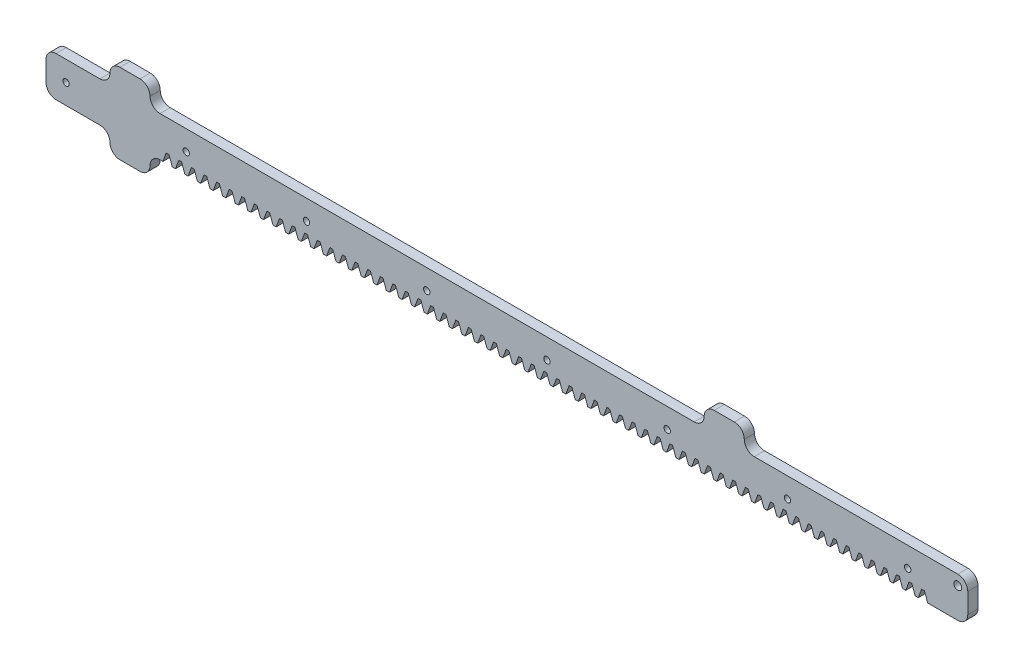
SolidWorks part; units mm, degrees
material "PC High Viscosity"
ref_plane "Front Plane" through (0, 0, 0) normal (0, 0, 1) x (1, 0, 0)
ref_plane "Top Plane" through (0, 0, 0) normal (0, 1, 0) x (1, 0, 0)
ref_plane "Right Plane" through (0, 0, 0) normal (1, 0, 0) x (0, 0, -1)
sketch "Sketch1" plane through (0, 0, 0) normal (0, 0, 1) x (1, 0, 0)
  line L1 (0, 0) -> (40.5308, 0)
  line L2 (0, 0) -> (0, 25.4)
  line L3 (0, 25.4) -> (40.5308, 25.4)
  line L4 (584.2, 0) -> (584.2, 25.4)
  line L7 (533.4, 25.4) -> (584.2, 25.4)
  line L8 (65.9308, 25.4) -> (417.1409, 25.4)
  line L9 (65.9308, 0) -> (584.2, 0)
  line L11 (584.2, 22.7162) -> (577.85, 26.3823) construction
  line L12 (577.85, 26.3823) -> (571.5, 22.7162) construction
  line L13 (571.5, 22.7162) -> (571.5, 15.3838) construction
  line L14 (571.5, 15.3838) -> (577.85, 11.7177) construction
  line L15 (577.85, 11.7177) -> (584.2, 15.3838) construction
  line L16 (584.2, 15.3838) -> (584.2, 22.7162) construction
  line L19 (590.55, 0) -> (590.55, 10.0162) construction
  line L20 (590.55, 10.0162) -> (76.2, 10.0162) construction
  line L21 (76.2, 10.0162) -> (76.2, 0) construction
  line L22 (442.5409, 25.4) -> (533.4, 25.4)
  line L23 (40.5308, 25.4) -> (40.5308, 38.1)
  line L24 (40.5308, 38.1) -> (65.9308, 38.1)
  line L25 (65.9308, 38.1) -> (65.9308, 25.4)
  line L26 (40.5308, 0) -> (40.5308, -12.7)
  line L27 (40.5308, -12.7) -> (65.9308, -12.7)
  line L28 (65.9308, -12.7) -> (65.9308, 0)
  line L29 (417.1409, 25.4) -> (417.1409, 38.1)
  line L30 (417.1409, 38.1) -> (442.5409, 38.1)
  line L31 (442.5409, 38.1) -> (442.5409, 25.4)
  circle A0 centre (577.85, 19.05) radius 2.4892
  circle A1 centre (577.85, 19.05) radius 6.35 construction
  point P6 (0, 0)
  point P7 (40.5308, 0)
  point P10 (577.85, 26.7355)
  point P29 (0, 0)
  dimension "D5" = 4.9784
  dimension "D6" = 25.4
  dimension "D7" = 12.7
  dimension "D1" = 584.2
  dimension "D2" = 25.4
  dimension "D3" = 167.0591
  dimension "D4" = 40.5308
  dimension "D8" = 12.7
extrude "Boss-Extrude1" add sketch "Sketch1" along normal blind 6.477 contours L3 | L1 L4 L3 L2 A0 | L1 region at (284.8004, 13.0814, 0)
fillet "Fillet2" radius 6.35 16 edges at (0, 0, 3.2385) (0, 25.4, 3.2385) (584.2, 25.4, 3.2385) (417.1409, 38.1, 3.2385) (442.5409, 38.1, 3.2385) (40.5308, 38.1, 3.2385) (65.9308, 38.1, 3.2385) (40.5308, 25.4, 3.2385) (40.5308, 0, 3.2385) (584.2, 0, 3.2385) (65.9308, 0, 3.2385) (65.9308, -12.7, 3.2385) (40.5308, -12.7, 3.2385) (65.9308, 25.4, 3.2385) (442.5409, 25.4, 3.2385) (417.1409, 25.4, 3.2385)
sketch "Sketch2" plane through (0, 0, 6.477) normal (0, 0, 1) x (1, 0, 0)
  line L0 (558.8, 0) -> (72.2808, 0)
  line L1 (72.2808, 0) -> (72.2808, 5.715)
  line L2 (72.2808, 5.715) -> (558.8, 5.715)
  line L3 (558.8, 5.715) -> (558.8, 0)
  line L5 (557.8755, 2.54) -> (549.711, 2.54) construction
  line L6 (558.8, 0) -> (556.7199, 5.715)
  line L8 (552.8688, 0) -> (558.8, 0)
  line L10 (556.7199, 5.715) -> (554.9488, 5.715)
  line L11 (558.8, 0) -> (552.8688, 0)
  line L12 (552.8688, 0) -> (554.9488, 5.715)
  line L13 (554.9488, 5.715) -> (556.7199, 5.715)
  line L14 (558.8, 0) -> (552.8688, 0)
  line L15 (554.9488, 5.715) -> (556.7199, 5.715)
  line L16 (558.8, 0) -> (552.8688, 0)
  line L17 (552.8688, 0) -> (558.8, 0)
  line L19 (556.7199, 5.715) -> (554.9488, 5.715) construction
  line L20 (552.8688, 0) -> (558.8, 0) construction
  line L21 (0, 0) -> (40.5308, 0) construction
  line L22 (584.2, 0) -> (584.2, 25.4) construction
  line L23 (65.9308, 0) -> (584.2, 0) construction
  point P8 (553.7932, 2.54)
  point P13 (552.8688, 0)
  point P15 (0, 0)
  point P16 (557.8755, 2.54)
  point P17 (571.6333, 0)
  point P21 (572.7128, -2.7117)
  point P22 (0, 0)
  point P23 (0, 0)
  point P24 (0, 0)
  point P25 (73.7246, 0)
  point P28 (72.2808, 0)
  point P30 (0, 0)
  point P32 (72.2808, 0)
  dimension "D1" = 70
  dimension "D2" = 2.54
  dimension "D3" = 3.175
  dimension "D4" = 70
  dimension "D5" = 1.7711
  dimension "D6" = 25.4
extrude "Cut-Extrude1" cut sketch "Sketch2" against normal through all contours L12 L0 L8 L6 L2 region at (555.8344, 2.343, 6.477)
pattern_linear "LPattern1" count 61 spacing 7.9796 along (-1, 0, 0) of "Cut-Extrude1"
sketch "Sketch3" plane through (0, 0, 6.477) normal (0, 0, 1) x (1, 0, 0)
  line L2 (533.4, 25.4) -> (584.2, 25.4) construction
  line L3 (584.2, 0) -> (584.2, 25.4) construction
  circle A0 centre (546.1, 12.7) radius 2.0193
  dimension "D2" = 4.0386
  dimension "D1" = 12.7
  dimension "D3" = 38.1
extrude "Cut-Extrude2" cut sketch "Sketch3" against normal through all
pattern_linear "LPattern2" count 8 spacing 76.2 along (-1, 0, 0) of "Cut-Extrude2"
